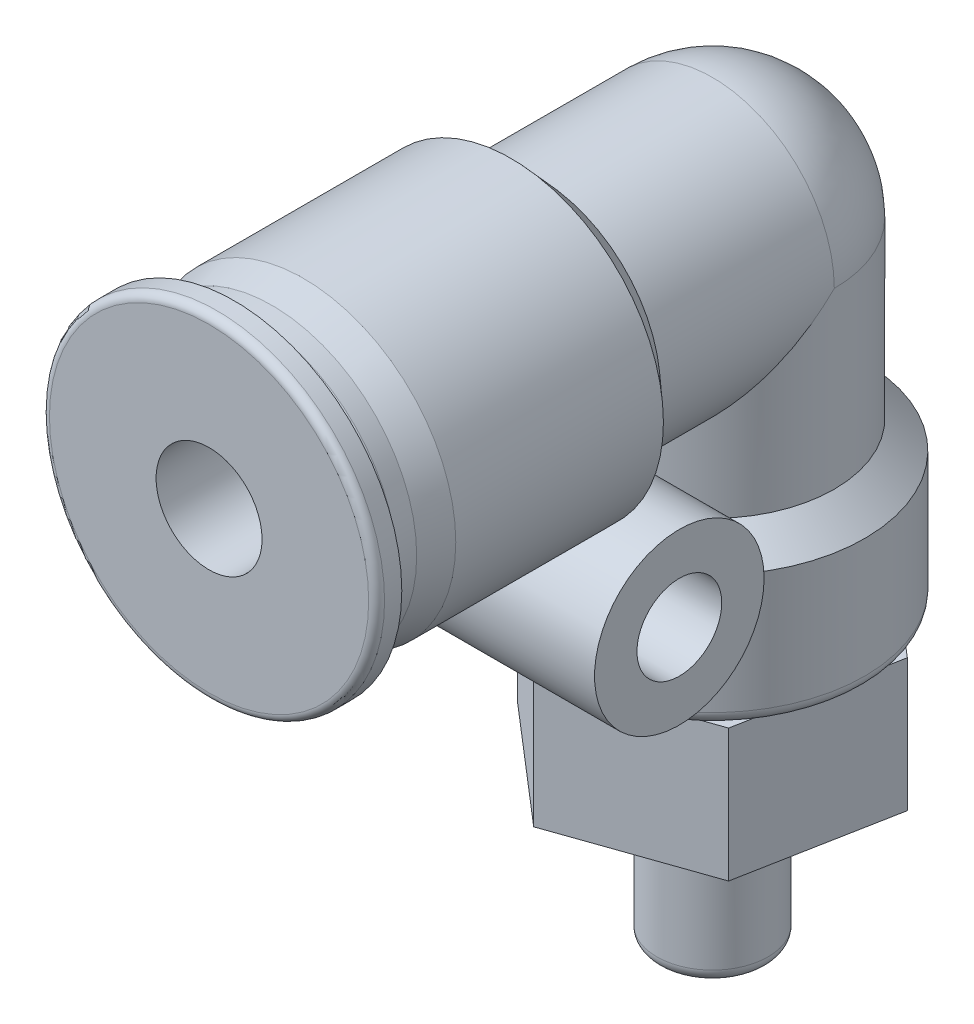
SolidWorks part; units mm, degrees
ref_plane "前视基准面" through (0, 0, 0) normal (0, 0, 1) x (1, 0, 0)
ref_plane "上视基准面" through (0, 0, 0) normal (0, 1, 0) x (1, 0, 0)
ref_plane "右视基准面" through (0, 0, 0) normal (1, 0, 0) x (0, 0, -1)
sketch "草图1" plane through (0, 0, 0) normal (1, 0, 0) x (0, 0, -1)
  line L0 (-19, 0) -> (-19, 6.025)
  line L1 (-18.7, 6.325) -> (-18.05, 6.325)
  line L2 (-18.05, 6.325) -> (-18.05, 3)
  line L3 (-18.05, 3) -> (-17.575, 3)
  line L4 (-17.575, 3) -> (-17.575, 5.2625)
  line L5 (-17.375, 5.4625) -> (-16.625, 5.4625)
  line L6 (-16.625, 5.4625) -> (-15.4375, 5.75)
  line L7 (-15.4375, 5.75) -> (-7.6, 5.75)
  line L8 (-7.6, 5.75) -> (-6.5645, 4.6)
  line L9 (-6.5645, 4.6) -> (0, 4.6)
  line L10 (4.6, 0) -> (-19, 0)
  line L11 (4.6, 0) -> (-19, 0) construction
  arc A0 (-19, 6.025) -> (-18.7, 6.325) centre (-18.7, 6.025) cw
  arc A1 (-17.575, 5.2625) -> (-17.375, 5.4625) centre (-17.375, 5.2625) cw
  arc A2 (0, 4.6) -> (4.6, 0) centre (0, 0) cw
revolve "旋转1" add sketch "草图1" angle 360 about L11 reverse direction yes
sketch "草图2" plane through (0, 0, 0) normal (1, 0, 0) x (0, 0, -1)
  line L7 (-5.75, -12.6) -> (-5.75, -7.6)
  line L8 (-5.75, -7.6) -> (-4.6, -6.5645)
  line L9 (-4.6, -6.5645) -> (-4.6, 0)
  line L10 (-4.6, 0) -> (0, 0)
  line L11 (0, 0) -> (0, -23.6)
  line L12 (0, 0) -> (0, -23.6) construction
  line L13 (-5.75, -12.6) -> (-2.1, -12.6)
  line L14 (-2.1, -12.6) -> (-2.1, -23.6)
  line L15 (-2.1, -23.6) -> (0, -23.6)
  dimension "D1" = 2.1
  dimension "D2" = 11
  dimension "D3" = 5
revolve "旋转2" add sketch "草图2" angle 360 about L12 reverse direction yes
sketch "草图3" plane through (0, 0, 0) normal (0, 0, 1) x (1, 0, 0)
  circle A0 centre (0, 0) radius 2
extrude "切除-拉伸1" cut sketch "草图3" along normal blind 19
sketch "草图4" plane through (0, 0, 0) normal (1, 0, 0) x (0, 0, -1)
  line L0 (2, 0) -> (2, -19)
  line L1 (2, -19) -> (0, -19)
  line L2 (0, -19) -> (0, 2)
  line L3 (0, -19) -> (0, 2) construction
  arc A0 (0, 2) -> (2, 0) centre (0, 0) cw
revolve "切除-旋转1" cut sketch "草图4" angle 360 about L3 reverse direction yes
sketch "草图5" plane through (0, 0, 0) normal (1, 0, 0) x (0, 0, -1)
  circle A0 centre (-7, -7) radius 3.2
extrude "凸台-拉伸1" add sketch "草图5" against normal blind 5.75 and the other way blind 5.75
sketch "草图6" plane through (0, 0, 0) normal (1, 0, 0) x (0, 0, -1)
  circle A0 centre (-7, -7) radius 1.6
extrude "切除-拉伸2" cut sketch "草图6" along normal blind 5.75 and the other way blind 5.75
fillet "圆角1" radius 0.5 2 edges at (0, -12.6, -5.75) (0, -23.6, -2.1)
sketch "草图7" plane through (0, -12.6, 0) normal (0, -1, 0) x (1, 0, 0)
  line L1 (5.4497, -1.9063) -> (4.3758, 3.7664)
  line L2 (4.3758, 3.7664) -> (-1.0739, 5.6727)
  line L3 (-1.0739, 5.6727) -> (-5.4497, 1.9063)
  line L4 (-5.4497, 1.9063) -> (-4.3758, -3.7664)
  line L5 (-4.3758, -3.7664) -> (1.0739, -5.6727)
  line L6 (1.0739, -5.6727) -> (5.4497, -1.9063)
  circle A0 centre (0, 0) radius 5 construction
  dimension "D1" = 10
extrude "凸台-拉伸2" add sketch "草图7" along normal blind 5
